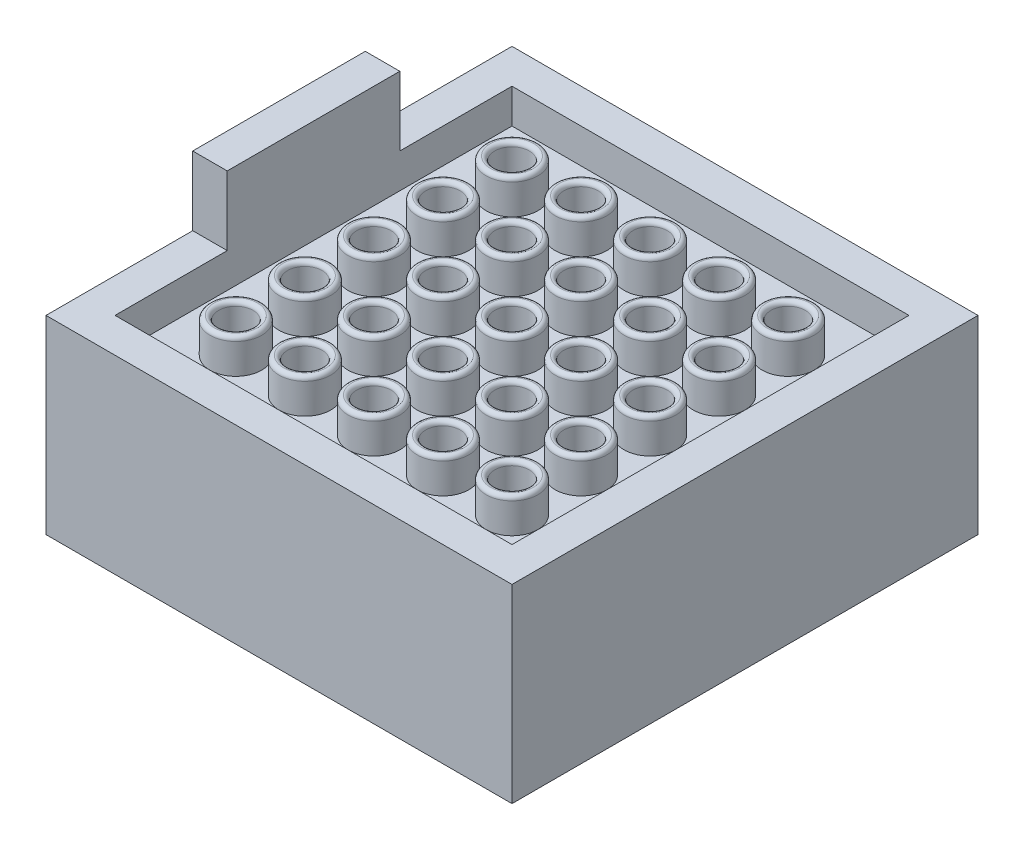
SolidWorks part; units mm, degrees
ref_plane "Front Plane" through (0, 0, 0) normal (0, 0, 1) x (1, 0, 0)
ref_plane "Top Plane" through (0, 0, 0) normal (0, 1, 0) x (1, 0, 0)
ref_plane "Right Plane" through (0, 0, 0) normal (1, 0, 0) x (0, 0, -1)
sketch "Sketch1" plane through (0, 0, 0) normal (0, 1, 0) x (1, 0, 0)
  line L0 (-13.5, 13.5) -> (13.5, 13.5)
  line L1 (-11.5, -11.5) -> (11.5, -11.5)
  line L2 (-11.5, -11.5) -> (-11.5, 11.5)
  line L3 (-11.5, 11.5) -> (11.5, 11.5)
  line L4 (11.5, -11.5) -> (11.5, 11.5)
  line L5 (-11.5, -11.5) -> (11.5, 11.5) construction
  line L6 (-11.5, 11.5) -> (11.5, -11.5) construction
  line L7 (13.5, -13.5) -> (13.5, 13.5)
  line L8 (-13.5, -13.5) -> (13.5, -13.5)
  line L9 (-13.5, -13.5) -> (-13.5, 13.5)
  point P0 (0, 0)
  dimension "D1" = 23
  dimension "D2" = 2
extrude "Boss-Extrude1" add sketch "Sketch1" along normal blind 2
sketch "Sketch2" plane through (0, 0, 0) normal (0, -1, 0) x (1, 0, 0)
  line L1 (-13.5, 13.5) -> (13.5, 13.5)
  line L2 (-13.5, 13.5) -> (-13.5, -13.5)
  line L3 (-13.5, -13.5) -> (13.5, -13.5)
  line L4 (13.5, 13.5) -> (13.5, -13.5)
  line L5 (-13.5, 13.5) -> (13.5, -13.5) construction
  line L6 (-13.5, -13.5) -> (13.5, 13.5) construction
  point P0 (0, 0)
extrude "Boss-Extrude2" add sketch "Sketch2" along normal blind 2
sketch "Sketch3" plane through (0, -2, 0) normal (0, -1, 0) x (1, 0, 0)
  line L0 (-11.5, 11.5) -> (11.5, 11.5)
  line L1 (-13.5, -13.5) -> (13.5, -13.5)
  line L2 (-13.5, -13.5) -> (-13.5, 13.5)
  line L3 (-13.5, 13.5) -> (13.5, 13.5)
  line L4 (13.5, -13.5) -> (13.5, 13.5)
  line L5 (-13.5, -13.5) -> (13.5, 13.5) construction
  line L6 (-13.5, 13.5) -> (13.5, -13.5) construction
  line L7 (11.5, -11.5) -> (11.5, 11.5)
  line L8 (-11.5, -11.5) -> (11.5, -11.5)
  line L9 (-11.5, -11.5) -> (-11.5, 11.5)
  point P0 (0, 0)
  dimension "D1" = 2
extrude "Boss-Extrude3" add sketch "Sketch3" along normal blind 5
sketch "Sketch6" plane through (0, 0, 0) normal (0, 1, 0) x (1, 0, 0)
  line L0 (11.5, -11.5) -> (11.5, 11.5) construction
  line L1 (11.5, 11.5) -> (-11.5, 11.5) construction
  circle A0 centre (8, 8) radius 1.5
  dimension "D2" = 3
  dimension "D1" = 3.5
  dimension "D3" = 3.5
extrude "Boss-Extrude5" add sketch "Sketch6" along normal blind 2
sketch "Sketch7" plane through (0, 2, 0) normal (0, 1, 0) x (1, 0, 0)
  circle A0 centre (8, 8) radius 1
  dimension "D1" = 2
extrude "Cut-Extrude2" cut sketch "Sketch7" against normal up to next
fillet "Fillet1" radius 0.25 2 edges at (8, 2, -6.5) (8, 2, -7)
pattern_linear "LPattern3" count 5 spacing 4 along (0, 0, 1) count 5 spacing 4 along (-1, 0, 0) of "Boss-Extrude5", "Cut-Extrude2", "Fillet1"
sketch "Sketch11" plane through (0, -2, 0) normal (0, -1, 0) x (1, 0, 0)
  line L0 (11.5, 11.5) -> (-11.5, 11.5) construction
  line L1 (-11.5, 11.5) -> (-11.5, -11.5) construction
  circle A0 centre (-9.9, 9.9) radius 0.75
  dimension "D1" = 1.5
  dimension "D3" = 1.6
  dimension "D2" = 1.6
extrude "Boss-Extrude8" add sketch "Sketch11" along normal up to surface (5 mm away) up to face at (0, -7, 0)
pattern_linear "LPattern2" count 6 spacing 4 along (1, 0, 0) count 6 spacing 4 along (0, 0, -1) of "Boss-Extrude8"
sketch "Sketch8" plane through (0, -7, 0) normal (0, -1, 0) x (1, 0, 0)
  line L1 (-13.5, -13.5) -> (13.5, -13.5)
  line L2 (-13.5, -13.5) -> (-13.5, 13.5)
  line L3 (-13.5, 13.5) -> (13.5, 13.5)
  line L4 (13.5, -13.5) -> (13.5, 13.5)
  line L5 (-13.5, -13.5) -> (13.5, 13.5) construction
  line L6 (-13.5, 13.5) -> (13.5, -13.5) construction
  point P0 (0, 0)
extrude "Boss-Extrude6" add sketch "Sketch8" along normal blind 2
sketch "Sketch9" plane through (0, -9, 0) normal (0, -1, 0) x (1, 0, 0)
  circle A0 centre (0, 0) radius 4.25
  dimension "D1" = 8.5
extrude "Cut-Extrude3" cut sketch "Sketch9" against normal blind 7
sketch "Sketch10" plane through (0, 2, 0) normal (0, 1, 0) x (1, 0, 0)
  line L0 (-13.5, 0) -> (-11.5, 0) construction
  line L1 (-13.5, 13.5) -> (-13.5, -13.5) construction
  line L2 (-11.5, 11.5) -> (-11.5, -11.5) construction
  line L4 (-11.5, 5) -> (-13.5, 5)
  line L5 (-11.5, 5) -> (-11.5, -5)
  line L6 (-11.5, -5) -> (-13.5, -5)
  line L7 (-13.5, 5) -> (-13.5, -5)
  line L8 (-11.5, 5) -> (-13.5, -5) construction
  line L9 (-11.5, -5) -> (-13.5, 5) construction
  point P6 (-12.5, 0)
  dimension "D1" = 10
extrude "Boss-Extrude7" add sketch "Sketch10" along normal blind 4
equation "\"D3@Sketch6\"=\"D1@Sketch6\""
equation "\"D3@Sketch11\"=\"D2@Sketch11\""
